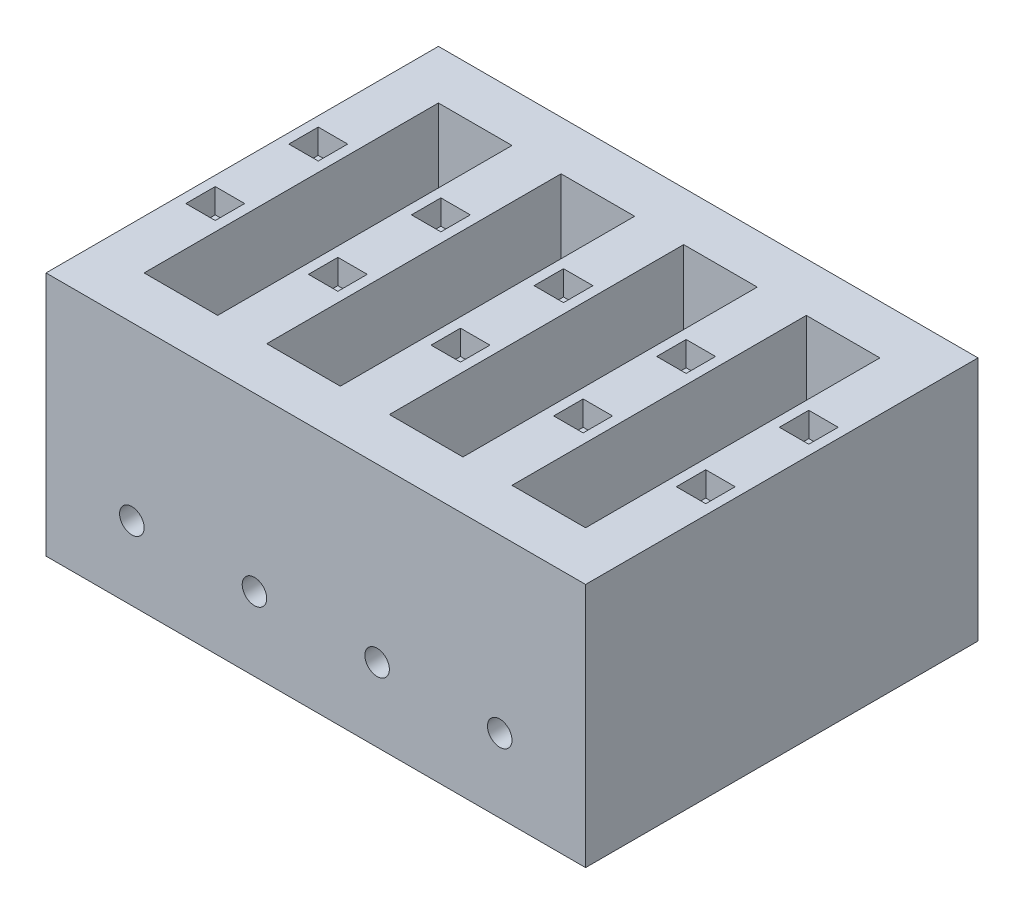
SolidWorks part; units mm, degrees
ref_plane "Front Plane" through (0, 0, 0) normal (0, 0, 1) x (1, 0, 0)
ref_plane "Top Plane" through (0, 0, 0) normal (0, 1, 0) x (1, 0, 0)
ref_plane "Right Plane" through (0, 0, 0) normal (1, 0, 0) x (0, 0, -1)
sketch "Sketch1" plane through (0, 0, 0) normal (0, 0, 1) x (1, 0, 0)
  line L1 (0, 0) -> (110, 0)
  line L2 (0, 0) -> (0, 50)
  line L3 (0, 50) -> (110, 50)
  line L4 (110, 0) -> (110, 50)
  dimension "D1" = 110
  dimension "D2" = 50
extrude "Boss-Extrude1" add sketch "Sketch1" against normal blind 80
ref_plane "Plane1" through (0, 0, -40) normal (0, 0, 1) x (1, 0, 0)
sketch "Sketch2" plane through (0, 50, 0) normal (0, 1, 0) x (1, 0, 0)
  line L1 (10, 10) -> (25, 10)
  line L2 (10, 10) -> (10, 20)
  line L3 (10, 70) -> (25, 70)
  line L4 (25, 10) -> (25, 20)
  line L16 (0, 80) -> (0, 0) construction
  line L17 (110, 0) -> (0, 0) construction
  line L18 (0, 40) -> (128.2216, 40) construction
  line L31 (10, 10) -> (35, 10) construction
  line L32 (10, 60) -> (10, 70)
  line L33 (10, 60) -> (25, 60)
  line L35 (10, 20) -> (25, 20)
  line L37 (25, 60) -> (25, 70)
  line L38 (35, 10) -> (50, 10)
  line L39 (50, 10) -> (50, 20)
  line L40 (35, 20) -> (50, 20)
  line L41 (35, 10) -> (35, 20)
  line L42 (35, 70) -> (50, 70)
  line L43 (50, 60) -> (50, 70)
  line L44 (35, 60) -> (50, 60)
  line L45 (35, 60) -> (35, 70)
  line L46 (60, 10) -> (75, 10)
  line L47 (75, 10) -> (75, 20)
  line L48 (60, 20) -> (75, 20)
  line L49 (60, 10) -> (60, 20)
  line L50 (60, 70) -> (75, 70)
  line L51 (75, 60) -> (75, 70)
  line L52 (60, 60) -> (75, 60)
  line L53 (60, 60) -> (60, 70)
  line L54 (85, 10) -> (100, 10)
  line L55 (100, 10) -> (100, 20)
  line L56 (85, 20) -> (100, 20)
  line L57 (85, 10) -> (85, 20)
  line L58 (85, 70) -> (100, 70)
  line L59 (100, 60) -> (100, 70)
  line L60 (85, 60) -> (100, 60)
  line L61 (85, 60) -> (85, 70)
  line L62 (10, 10) -> (35, 10) construction
  point P7 (0, 40)
  dimension "D1" = 15
  dimension "D2" = 60
  dimension "D4" = 10
  dimension "D5" = 10
  dimension "D6" = 25
  dimension "D7" = 10
  dimension "D8" = 10
  dimension "D9" = 25
  dimension "D3" = 4
extrude "Cut-Extrude1" cut sketch "Sketch2" against normal blind 40
sketch "Sketch4" plane through (0, 0, 0) normal (0, 0, 1) x (1, 0, 0)
  line L0 (0, 50) -> (0, 0) construction
  line L1 (110, 50) -> (0, 50) construction
  line L2 (17.5, 15) -> (42.5, 15) construction
  circle A0 centre (17.5, 15) radius 2.5
  circle A1 centre (42.5, 15) radius 2.5
  circle A2 centre (67.5, 15) radius 2.5
  circle A3 centre (92.5, 15) radius 2.5
  dimension "D3" = 5
  dimension "D1" = 17.5
  dimension "D2" = 35
  dimension "D5" = 25
  dimension "D4" = 4
extrude "Cut-Extrude2" cut sketch "Sketch4" against normal blind 10
mirror "Mirror1" about plane through (0, 0, -40) normal (0, 0, 1) of "Cut-Extrude2"
sketch "Sketch5" plane through (0, 50, 0) normal (0, 1, 0) x (1, 0, 0)
  line L0 (35, 20) -> (35, 60)
  line L1 (10, 20) -> (25, 20)
  line L2 (10, 20) -> (10, 60)
  line L3 (10, 60) -> (25, 60)
  line L4 (25, 20) -> (25, 60)
  line L5 (35, 20) -> (50, 20)
  line L6 (50, 20) -> (50, 60)
  line L7 (35, 60) -> (50, 60)
  line L8 (60, 20) -> (60, 60)
  line L9 (60, 20) -> (75, 20)
  line L10 (75, 20) -> (75, 60)
  line L11 (60, 60) -> (75, 60)
  line L12 (85, 20) -> (85, 60)
  line L13 (85, 20) -> (100, 20)
  line L14 (100, 20) -> (100, 60)
  line L15 (85, 60) -> (100, 60)
  line L16 (10, 20) -> (35, 20) construction
  dimension "D2" = 25
  dimension "D1" = 4
extrude "Cut-Extrude3" cut sketch "Sketch5" against normal blind 15
sketch "Sketch6" plane through (0, 50, 0) normal (0, 1, 0) x (1, 0, 0)
  line L1 (2, 47.5) -> (8, 47.5)
  line L2 (2, 47.5) -> (2, 53.5)
  line L3 (2, 53.5) -> (8, 53.5)
  line L4 (8, 47.5) -> (8, 53.5)
  line L5 (0, 80) -> (0, 0) construction
  line L6 (-27.5, 40) -> (27.5, 40) construction
  line L7 (27, 47.5) -> (27, 53.5)
  line L8 (27, 47.5) -> (33, 47.5)
  line L9 (33, 47.5) -> (33, 53.5)
  line L10 (27, 53.5) -> (33, 53.5)
  line L11 (52, 47.5) -> (52, 53.5)
  line L12 (52, 47.5) -> (58, 47.5)
  line L13 (58, 47.5) -> (58, 53.5)
  line L14 (52, 53.5) -> (58, 53.5)
  line L15 (77, 47.5) -> (77, 53.5)
  line L16 (77, 47.5) -> (83, 47.5)
  line L17 (83, 47.5) -> (83, 53.5)
  line L18 (77, 53.5) -> (83, 53.5)
  line L19 (102, 47.5) -> (102, 53.5)
  line L20 (102, 47.5) -> (108, 47.5)
  line L21 (108, 47.5) -> (108, 53.5)
  line L22 (102, 53.5) -> (108, 53.5)
  line L23 (27, 26.5) -> (27, 32.5)
  line L24 (27, 26.5) -> (33, 26.5)
  line L25 (33, 26.5) -> (33, 32.5)
  line L26 (27, 32.5) -> (33, 32.5)
  line L27 (52, 26.5) -> (52, 32.5)
  line L28 (52, 26.5) -> (58, 26.5)
  line L29 (58, 26.5) -> (58, 32.5)
  line L30 (52, 32.5) -> (58, 32.5)
  line L31 (77, 26.5) -> (77, 32.5)
  line L32 (77, 26.5) -> (83, 26.5)
  line L33 (83, 26.5) -> (83, 32.5)
  line L34 (77, 32.5) -> (83, 32.5)
  line L35 (102, 26.5) -> (102, 32.5)
  line L36 (102, 26.5) -> (108, 26.5)
  line L37 (108, 26.5) -> (108, 32.5)
  line L38 (102, 32.5) -> (108, 32.5)
  line L39 (2, 26.5) -> (2, 32.5)
  line L40 (2, 26.5) -> (8, 26.5)
  line L41 (8, 26.5) -> (8, 32.5)
  line L42 (2, 32.5) -> (8, 32.5)
  line L43 (2, 47.5) -> (27, 47.5) construction
  dimension "D1" = 6
  dimension "D2" = 6
  dimension "D3" = 2
  dimension "D4" = 7.5
  dimension "D7" = 25
  dimension "D5" = 5
  dimension "D6" = 2
extrude "Cut-Extrude4" cut sketch "Sketch6" against normal blind 5
